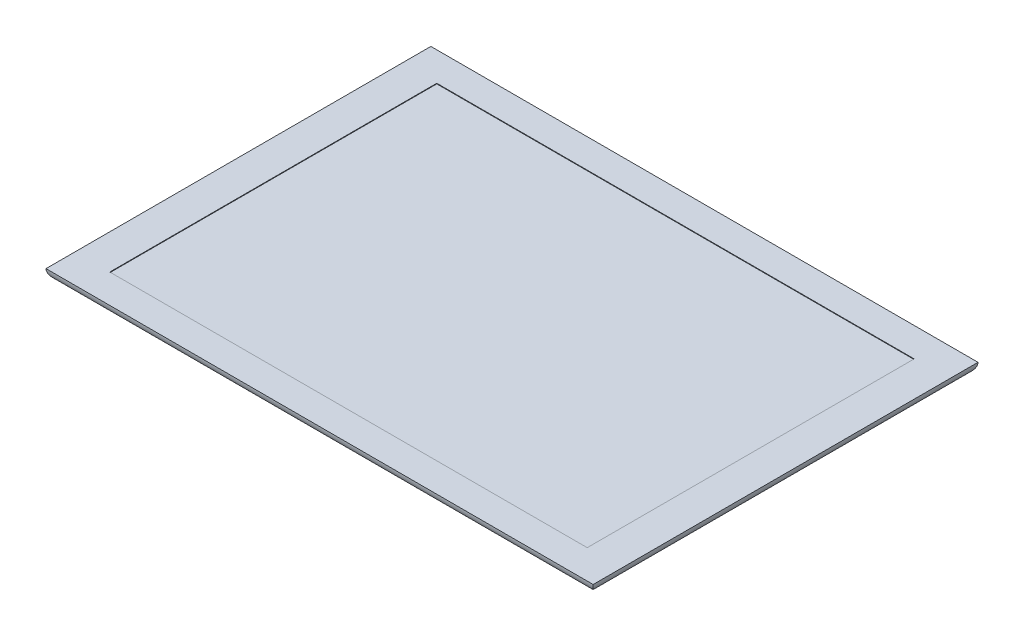
SolidWorks part; units mm, degrees
ref_plane "Front Plane" through (0, 0, 0) normal (0, 0, 1) x (1, 0, 0)
ref_plane "Top Plane" through (0, 0, 0) normal (0, 1, 0) x (1, 0, 0)
ref_plane "Right Plane" through (0, 0, 0) normal (1, 0, 0) x (0, 0, -1)
sketch "Sketch1" plane through (0, 0, 0) normal (0, 1, 0) x (1, 0, 0)
  line L1 (-187.325, -131.7625) -> (187.325, -131.7625)
  line L2 (-187.325, -131.7625) -> (-187.325, 131.7625)
  line L3 (-187.325, 131.7625) -> (187.325, 131.7625)
  line L4 (187.325, -131.7625) -> (187.325, 131.7625)
  line L5 (-187.325, -131.7625) -> (187.325, 131.7625) construction
  line L6 (-187.325, 131.7625) -> (187.325, -131.7625) construction
  line L7 (-163.4583, -111.9505) -> (163.4583, -111.9505)
  line L8 (-163.4583, -111.9505) -> (-163.4583, 111.9505)
  line L9 (-163.4583, 111.9505) -> (163.4583, 111.9505)
  line L10 (163.4583, -111.9505) -> (163.4583, 111.9505)
  line L11 (-163.4583, -111.9505) -> (163.4583, 111.9505) construction
  line L12 (-163.4583, 111.9505) -> (163.4583, -111.9505) construction
  point P0 (0, 0)
  point P6 (0, 0)
  dimension "D1" = 374.65
  dimension "D2" = 263.525
  dimension "D3" = 396.24
  dimension "D4" = 19.812
extrude "Boss-Extrude1" add sketch "Sketch1" along normal blind 7.5
extrude "Boss-Extrude2" add sketch "Sketch1<2>" along normal blind 7.1 contours L7 L10 L9 L8 region at (0, 0, 0)
sketch "Sketch1<2>" plane through (0, 0, 0) normal (0, 1, 0) x (1, 0, 0) same geometry as "Sketch1"
fillet "Fillet1" radius 7.62 1 edges at (0, 0, -131.7625)
fillet "Fillet2" radius 7.62 3 edges at (-187.325, 0, 3.8095) (187.325, 0, 3.8095) (0, 0, 131.7625)
